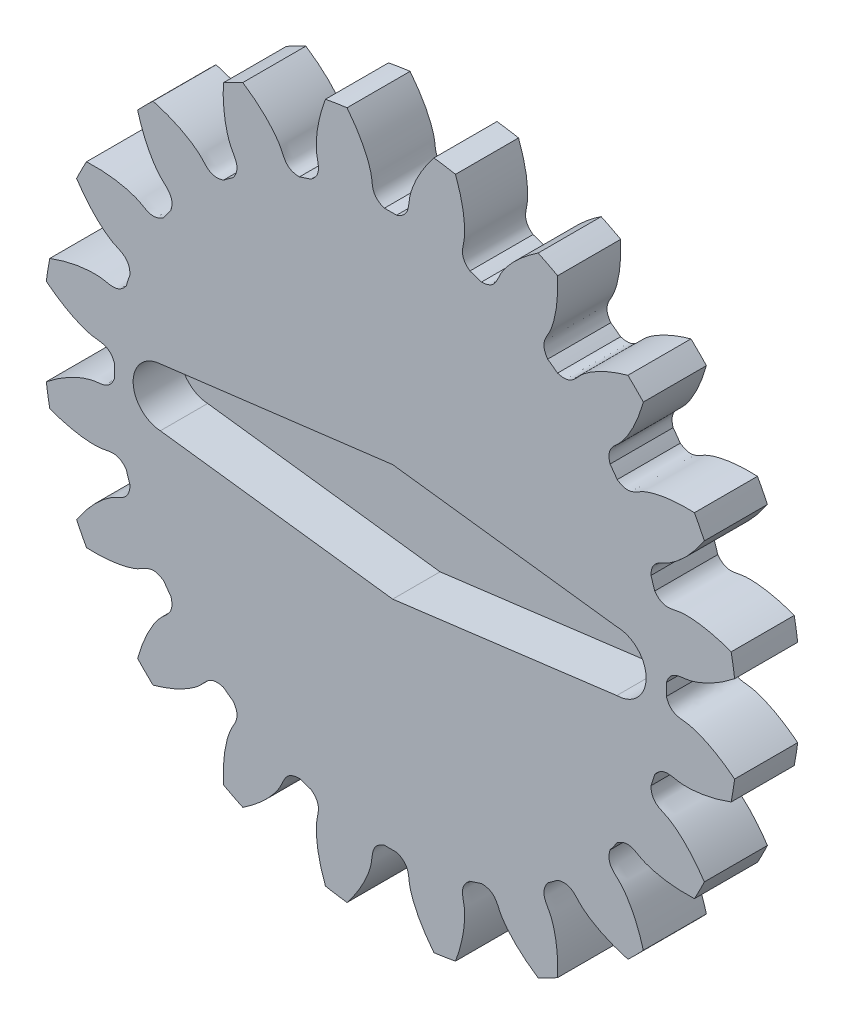
SolidWorks part; units mm, degrees
ref_plane "前视基准面" through (0, 0, 0) normal (0, 0, 1) x (1, 0, 0)
ref_plane "上视基准面" through (0, 0, 0) normal (0, 1, 0) x (1, 0, 0)
ref_plane "右视基准面" through (0, 0, 0) normal (1, 0, 0) x (0, 0, -1)
sketch "草图1" plane through (0, 0, 0) normal (0, 0, 1) x (1, 0, 0)
  circle A0 centre (0, 0) radius 22
extrude "凸台-拉伸1" add sketch "草图1" along normal blind 30
ref_axis "基准轴1" through (0, 0, -1.5) along (0, 0, 1)
sketch "草图2" plane through (0, 0, 0) normal (0, 0, 1) x (1, 0, 0)
  line L0 (0, 0) -> (0, 22) construction
  circle A0 centre (0, 0) radius 22 construction
  arc A1 (0.3866, 17.4957) -> (-0.3866, 17.4957) centre (0, 0) ccw
  arc A2 (6.3623, 24.9965) -> (-6.3623, 24.9965) centre (0, 0) ccw
  spline S0 degree 3 poles (0.3866, 17.4957) (1.2224, 17.787) (1.1142, 18.3742) (1.2258, 18.94) (1.2378, 18.9951) (1.2526, 19.0573) (1.2706, 19.1264) (1.292, 19.2024) (1.317, 19.2851) (1.3461, 19.3745) (1.3793, 19.4704) (1.4171, 19.5726) (1.4597, 19.6811) (1.5073, 19.7956) (1.5603, 19.9161) (1.6187, 20.0423) (1.683, 20.174) (1.7534, 20.3112) (1.83, 20.4535) (1.9132, 20.6008) (2.0031, 20.7529) (2.1, 20.9095) (2.204, 21.0705) (2.3155, 21.2356) (2.4346, 21.4046) (2.5615, 21.5772) (2.6964, 21.7533) (2.8395, 21.9324) (2.991, 22.1145) (3.1509, 22.2992) (3.3196, 22.4862) (3.4971, 22.6753) (3.6837, 22.8662) (3.8793, 23.0586) (4.0843, 23.2521) (4.2986, 23.4467) (4.5225, 23.6418) (4.7559, 23.8372) (4.9991, 24.0327) (5.2521, 24.2278) (5.515, 24.4223) (5.8829, 24.6833) (6.1679, 24.8727) (6.3623, 24.9965) knots 0 0 0 0 0.165916 0.170906 0.176664 0.183189 0.190482 0.198542 0.207371 0.216967 0.22733 0.238462 0.250361 0.263027 0.276462 0.290664 0.305634 0.321371 0.337876 0.355149 0.37319 0.391998 0.411574 0.431917 0.453028 0.474907 0.497554 0.520968 0.54515 0.570099 0.595817 0.622302 0.649554 0.677575 0.706363 0.735918 0.766242 0.797333 0.829191 0.861818 0.895212 0.929373 1 1 1 1
  spline S1 degree 3 poles (-0.3866, 17.4957) (-1.2224, 17.787) (-1.1142, 18.3742) (-1.2258, 18.94) (-1.2378, 18.9951) (-1.2526, 19.0573) (-1.2706, 19.1264) (-1.292, 19.2024) (-1.317, 19.2851) (-1.3461, 19.3745) (-1.3793, 19.4704) (-1.4171, 19.5726) (-1.4597, 19.6811) (-1.5073, 19.7956) (-1.5603, 19.9161) (-1.6187, 20.0423) (-1.683, 20.174) (-1.7534, 20.3112) (-1.83, 20.4535) (-1.9132, 20.6008) (-2.0031, 20.7529) (-2.1, 20.9095) (-2.204, 21.0705) (-2.3155, 21.2356) (-2.4346, 21.4046) (-2.5615, 21.5772) (-2.6964, 21.7533) (-2.8395, 21.9324) (-2.991, 22.1145) (-3.1509, 22.2992) (-3.3196, 22.4862) (-3.4971, 22.6753) (-3.6837, 22.8662) (-3.8793, 23.0586) (-4.0843, 23.2521) (-4.2986, 23.4467) (-4.5225, 23.6418) (-4.7559, 23.8372) (-4.9991, 24.0327) (-5.2521, 24.2278) (-5.515, 24.4223) (-5.8829, 24.6833) (-6.1679, 24.8727) (-6.3623, 24.9965) knots 0 0 0 0 0.165916 0.170906 0.176664 0.183189 0.190482 0.198542 0.207371 0.216967 0.22733 0.238462 0.250361 0.263027 0.276462 0.290664 0.305634 0.321371 0.337876 0.355149 0.37319 0.391998 0.411574 0.431917 0.453028 0.474907 0.497554 0.520968 0.54515 0.570099 0.595817 0.622302 0.649554 0.677575 0.706363 0.735918 0.766242 0.797333 0.829191 0.861818 0.895212 0.929373 1 1 1 1
extrude "切除-拉伸1" cut sketch "草图2" along normal through all
pattern_circular "阵列(圆周)1" count 20 every 18 about axis through (0, 0, -1.5) along (0, 0, 1) of "切除-拉伸1"
sketch "草图4" plane through (0, 0, 30) normal (0, 0, 1) x (1, 0, 0)
  line L0 (14.3305, 1.878) -> (0.1423, 3.6731)
  line L1 (0.1423, -3.7145) -> (14.354, -1.9038)
  line L2 (-14.5959, -1.8373) -> (0.1423, -3.7145)
  line L3 (0.1423, 3.6731) -> (-14.6311, 1.8342)
  circle A0 centre (0, 0) radius 0.8783 construction
  arc A1 (14.354, -1.9038) -> (14.3305, 1.878) centre (14.326, -0.013) ccw
  arc A2 (-14.6311, 1.8342) -> (-14.5959, -1.8373) centre (-14.4818, -0.0003) ccw
extrude "切除-拉伸2" cut sketch "草图4" against normal blind 3
sketch "草图6" plane through (0, 0, 0) normal (0, 0, -1) x (-1, 0, 0)
  arc A40 (5.7742, 16.52) -> (5.0388, 16.7589) centre (0, 0) ccw
  arc A41 (4.1243, 21.61) -> (2.7554, 21.8268) centre (0, 0) ccw
  arc A42 (0.3866, 17.4957) -> (-0.3866, 17.4957) centre (0, 0) ccw
  arc A43 (-2.7554, 21.8268) -> (-4.1243, 21.61) centre (0, 0) ccw
  arc A44 (-5.0388, 16.7589) -> (-5.7742, 16.52) centre (0, 0) ccw
  arc A45 (-9.3654, 19.907) -> (-10.6003, 19.2778) centre (0, 0) ccw
  arc A46 (-9.9709, 14.3816) -> (-10.5965, 13.9271) centre (0, 0) ccw
  arc A47 (-15.0586, 16.0386) -> (-16.0386, 15.0586) centre (0, 0) ccw
  arc A48 (-13.9271, 10.5965) -> (-14.3816, 9.9709) centre (0, 0) ccw
  arc A49 (-19.2778, 10.6003) -> (-19.907, 9.3654) centre (0, 0) ccw
  arc A50 (-16.52, 5.7742) -> (-16.7589, 5.0388) centre (0, 0) ccw
  arc A51 (-21.61, 4.1243) -> (-21.8268, 2.7554) centre (0, 0) ccw
  arc A52 (-17.4957, 0.3866) -> (-17.4957, -0.3866) centre (0, 0) ccw
  arc A53 (-21.8268, -2.7554) -> (-21.61, -4.1243) centre (0, 0) ccw
  arc A54 (-16.7589, -5.0388) -> (-16.52, -5.7742) centre (0, 0) ccw
  arc A55 (-19.907, -9.3654) -> (-19.2778, -10.6003) centre (0, 0) ccw
  arc A56 (-14.3816, -9.9709) -> (-13.9271, -10.5965) centre (0, 0) ccw
  arc A57 (-16.0386, -15.0586) -> (-15.0586, -16.0386) centre (0, 0) ccw
  arc A58 (-10.5965, -13.9271) -> (-9.9709, -14.3816) centre (0, 0) ccw
  arc A59 (-10.6003, -19.2778) -> (-9.3654, -19.907) centre (0, 0) ccw
  arc A60 (-5.7742, -16.52) -> (-5.0388, -16.7589) centre (0, 0) ccw
  arc A61 (-4.1243, -21.61) -> (-2.7554, -21.8268) centre (0, 0) ccw
  arc A62 (-0.3866, -17.4957) -> (0.3866, -17.4957) centre (0, 0) ccw
  arc A63 (2.7554, -21.8268) -> (4.1243, -21.61) centre (0, 0) ccw
  arc A64 (5.0388, -16.7589) -> (5.7742, -16.52) centre (0, 0) ccw
  arc A65 (9.3654, -19.907) -> (10.6003, -19.2778) centre (0, 0) ccw
  arc A66 (9.9709, -14.3816) -> (10.5965, -13.9271) centre (0, 0) ccw
  arc A67 (15.0586, -16.0386) -> (16.0386, -15.0586) centre (0, 0) ccw
  arc A68 (13.9271, -10.5965) -> (14.3816, -9.9709) centre (0, 0) ccw
  arc A69 (19.2778, -10.6003) -> (19.907, -9.3654) centre (0, 0) ccw
  arc A70 (16.52, -5.7742) -> (16.7589, -5.0388) centre (0, 0) ccw
  arc A71 (21.61, -4.1243) -> (21.8268, -2.7554) centre (0, 0) ccw
  arc A72 (17.4957, -0.3866) -> (17.4957, 0.3866) centre (0, 0) ccw
  arc A73 (21.8268, 2.7554) -> (21.61, 4.1243) centre (0, 0) ccw
  arc A74 (16.7589, 5.0388) -> (16.52, 5.7742) centre (0, 0) ccw
  arc A75 (19.907, 9.3654) -> (19.2778, 10.6003) centre (0, 0) ccw
  arc A76 (14.3816, 9.9709) -> (13.9271, 10.5965) centre (0, 0) ccw
  arc A77 (16.0386, 15.0586) -> (15.0586, 16.0386) centre (0, 0) ccw
  arc A78 (10.5965, 13.9271) -> (9.9709, 14.3816) centre (0, 0) ccw
  arc A79 (10.6003, 19.2778) -> (9.3654, 19.907) centre (0, 0) ccw
  arc A80 (5.7742, 16.52) -> (5.0388, 16.7589) centre (0, 0) ccw
  arc A81 (4.1243, 21.61) -> (2.7554, 21.8268) centre (0, 0) ccw
  arc A82 (0.3866, 17.4957) -> (-0.3866, 17.4957) centre (0, 0) ccw
  arc A83 (-2.7554, 21.8268) -> (-4.1243, 21.61) centre (0, 0) ccw
  arc A84 (-5.0388, 16.7589) -> (-5.7742, 16.52) centre (0, 0) ccw
  arc A85 (-9.3654, 19.907) -> (-10.6003, 19.2778) centre (0, 0) ccw
  arc A86 (-9.9709, 14.3816) -> (-10.5965, 13.9271) centre (0, 0) ccw
  arc A87 (-15.0586, 16.0386) -> (-16.0386, 15.0586) centre (0, 0) ccw
  arc A88 (-13.9271, 10.5965) -> (-14.3816, 9.9709) centre (0, 0) ccw
  arc A89 (-19.2778, 10.6003) -> (-19.907, 9.3654) centre (0, 0) ccw
  arc A90 (-16.52, 5.7742) -> (-16.7589, 5.0388) centre (0, 0) ccw
  arc A91 (-21.61, 4.1243) -> (-21.8268, 2.7554) centre (0, 0) ccw
  arc A92 (-17.4957, 0.3866) -> (-17.4957, -0.3866) centre (0, 0) ccw
  arc A93 (-21.8268, -2.7554) -> (-21.61, -4.1243) centre (0, 0) ccw
  arc A94 (-16.7589, -5.0388) -> (-16.52, -5.7742) centre (0, 0) ccw
  arc A95 (-19.907, -9.3654) -> (-19.2778, -10.6003) centre (0, 0) ccw
  arc A96 (-14.3816, -9.9709) -> (-13.9271, -10.5965) centre (0, 0) ccw
  arc A97 (-16.0386, -15.0586) -> (-15.0586, -16.0386) centre (0, 0) ccw
  arc A98 (-10.5965, -13.9271) -> (-9.9709, -14.3816) centre (0, 0) ccw
  arc A99 (-10.6003, -19.2778) -> (-9.3654, -19.907) centre (0, 0) ccw
  arc A100 (-5.7742, -16.52) -> (-5.0388, -16.7589) centre (0, 0) ccw
  arc A101 (-4.1243, -21.61) -> (-2.7554, -21.8268) centre (0, 0) ccw
  arc A102 (-0.3866, -17.4957) -> (0.3866, -17.4957) centre (0, 0) ccw
  arc A103 (2.7554, -21.8268) -> (4.1243, -21.61) centre (0, 0) ccw
  arc A104 (5.0388, -16.7589) -> (5.7742, -16.52) centre (0, 0) ccw
  arc A105 (9.3654, -19.907) -> (10.6003, -19.2778) centre (0, 0) ccw
  arc A106 (9.9709, -14.3816) -> (10.5965, -13.9271) centre (0, 0) ccw
  arc A107 (15.0586, -16.0386) -> (16.0386, -15.0586) centre (0, 0) ccw
  arc A108 (13.9271, -10.5965) -> (14.3816, -9.9709) centre (0, 0) ccw
  arc A109 (19.2778, -10.6003) -> (19.907, -9.3654) centre (0, 0) ccw
  arc A110 (16.52, -5.7742) -> (16.7589, -5.0388) centre (0, 0) ccw
  arc A111 (21.61, -4.1243) -> (21.8268, -2.7554) centre (0, 0) ccw
  arc A112 (17.4957, -0.3866) -> (17.4957, 0.3866) centre (0, 0) ccw
  arc A113 (21.8268, 2.7554) -> (21.61, 4.1243) centre (0, 0) ccw
  arc A114 (16.7589, 5.0388) -> (16.52, 5.7742) centre (0, 0) ccw
  arc A115 (19.907, 9.3654) -> (19.2778, 10.6003) centre (0, 0) ccw
  arc A116 (14.3816, 9.9709) -> (13.9271, 10.5965) centre (0, 0) ccw
  arc A117 (16.0386, 15.0586) -> (15.0586, 16.0386) centre (0, 0) ccw
  arc A118 (10.5965, 13.9271) -> (9.9709, 14.3816) centre (0, 0) ccw
  arc A119 (10.6003, 19.2778) -> (9.3654, 19.907) centre (0, 0) ccw
  spline S40 degree 3 poles (-3708.45, 1494.5416) (204.688, -113.6332) (40.2969, 43.5606) (8.612, 19.3644) (8.3225, 19.1244) (8.1035, 18.9276) (7.9087, 18.7415) (7.7679, 18.5988) (7.6102, 18.4289) (7.4979, 18.3006) (7.3961, 18.1768) (7.3285, 18.0912) (7.2672, 18.0103) (7.212, 17.9343) (7.1626, 17.8633) (7.1188, 17.7976) (7.0702, 17.7216) (7.029, 17.6528) (2.9985, 10.4296) (41.0631, -19.5683) (-3336.3667, 2212.5854) knots -11.584275 -11.584275 -11.584275 -11.584275 0.546972 0.588426 0.62681 0.662124 0.678629 0.709336 0.723538 0.749639 0.761538 0.77267 0.783033 0.792629 0.801458 0.809518 0.816811 0.829094 0.834084 3.350705 3.350705 3.350705 3.350705 only from (9.3654, 19.907) to (5.7742, 16.52)
  spline S41 degree 3 poles (4000.4369, -171.0805) (-44.7285, 8.305) (3.7044, 10.1997) (4.6895, 18.413) (4.6966, 18.4929) (4.702, 18.5829) (4.7051, 18.6618) (4.7069, 18.7482) (4.7069, 18.8422) (4.7048, 18.9437) (4.7005, 19.0526) (4.6909, 19.2127) (4.671, 19.4311) (4.6338, 19.7144) (4.5802, 20.0256) (4.508, 20.3639) (4.4148, 20.7281) (4.2986, 21.1171) (-9.4722, 61.2884) (-246.7896, 19.6625) (3881.4649, -959.8769) knots -2.350858 -2.350858 -2.350858 -2.350858 0.165916 0.170906 0.183189 0.190482 0.198542 0.207371 0.216967 0.22733 0.238462 0.250361 0.276462 0.305634 0.337876 0.37319 0.411574 0.453028 0.497554 13.418674 13.418674 13.418674 13.418674 only from (5.0388, 16.7589) to (4.1243, 21.61)
  spline S42 degree 3 poles (-3988.7843, 275.4194) (229.7845, -44.8196) (24.8636, 53.881) (2.2066, 21.0778) (2.0054, 20.7602) (1.8579, 20.5053) (1.7302, 20.2681) (1.6403, 20.0889) (1.5429, 19.8786) (1.4757, 19.7219) (1.4171, 19.5726) (1.3793, 19.4704) (1.3461, 19.3745) (1.317, 19.2851) (1.292, 19.2024) (1.2706, 19.1264) (1.2479, 19.0391) (1.2299, 18.9609) (-0.3711, 10.8457) (45.1002, -5.9213) (-3856.7998, 1073.2998) knots -11.584275 -11.584275 -11.584275 -11.584275 0.546972 0.588426 0.62681 0.662124 0.678629 0.709336 0.723538 0.749639 0.761538 0.77267 0.783033 0.792629 0.801458 0.809518 0.816811 0.829094 0.834084 3.350705 3.350705 3.350705 3.350705 only from (2.7554, 21.8268) to (0.3866, 17.4957)
  spline S43 degree 3 poles (3857.5084, 1073.4958) (-45.1057, -5.9234) (0.3712, 10.8453) (-1.2299, 18.9609) (-1.2479, 19.0391) (-1.2706, 19.1264) (-1.292, 19.2024) (-1.317, 19.2851) (-1.3461, 19.3745) (-1.3793, 19.4704) (-1.4171, 19.5726) (-1.4757, 19.7219) (-1.5621, 19.9235) (-1.6851, 20.1814) (-1.8322, 20.4609) (-2.0054, 20.7602) (-2.2066, 21.0778) (-2.4373, 21.4119) (-27.9477, 55.3617) (-240.7869, -57.562) (3988.1108, 286.5414) knots -2.350858 -2.350858 -2.350858 -2.350858 0.165916 0.170906 0.183189 0.190482 0.198542 0.207371 0.216967 0.22733 0.238462 0.250361 0.276462 0.305634 0.337876 0.37319 0.411574 0.453028 0.497554 13.418674 13.418674 13.418674 13.418674 only from (-0.3866, 17.4957) to (-2.7554, 21.8268)
  spline S44 degree 3 poles (-3878.6685, -970.6627) (232.388, 28.3814) (6.9966, 58.9272) (-4.4148, 20.7281) (-4.508, 20.3639) (-4.5695, 20.0759) (-4.6177, 19.8108) (-4.6478, 19.6126) (-4.6755, 19.3824) (-4.6909, 19.2127) (-4.7005, 19.0526) (-4.7048, 18.9437) (-4.7069, 18.8422) (-4.7069, 18.7482) (-4.7051, 18.6618) (-4.702, 18.5829) (-4.6966, 18.4929) (-4.6895, 18.413) (-3.7045, 10.2002) (44.7226, 8.3052) (-3999.7024, -171.0479) knots -11.584275 -11.584275 -11.584275 -11.584275 0.546972 0.588426 0.62681 0.662124 0.678629 0.709336 0.723538 0.749639 0.761538 0.77267 0.783033 0.792629 0.801458 0.809518 0.816811 0.829094 0.834084 3.350705 3.350705 3.350705 3.350705 only from (-4.1243, 21.61) to (-5.0388, 16.7589)
  spline S45 degree 3 poles (3336.9801, 2212.9908) (-41.0677, -19.5719) (-2.9983, 10.4292) (-7.029, 17.6528) (-7.0702, 17.7216) (-7.1188, 17.7976) (-7.1626, 17.8633) (-7.212, 17.9343) (-7.2672, 18.0103) (-7.3285, 18.0912) (-7.3961, 18.1768) (-7.4979, 18.3006) (-7.6424, 18.4656) (-7.839, 18.673) (-8.0653, 18.8932) (-8.3225, 19.1244) (-8.612, 19.3644) (-8.9347, 19.6108) (-43.6876, 44.0158) (-211.2143, -129.152) (3704.3726, 1504.9111) knots -2.350858 -2.350858 -2.350858 -2.350858 0.165916 0.170906 0.183189 0.190482 0.198542 0.207371 0.216967 0.22733 0.238462 0.250361 0.276462 0.305634 0.337876 0.37319 0.411574 0.453028 0.497554 13.418674 13.418674 13.418674 13.418674 only from (-5.7742, 16.52) to (-9.3654, 19.907)
  spline S46 degree 3 poles (-3388.8817, -2121.7296) (212.2438, 98.8041) (-11.5554, 58.2051) (-10.6041, 18.3493) (-10.5801, 17.9741) (-10.5496, 17.6812) (-10.5135, 17.4143) (-10.4809, 17.2164) (-10.4361, 16.989) (-10.3984, 16.8228) (-10.358, 16.6676) (-10.3285, 16.5626) (-10.2991, 16.4655) (-10.27, 16.3761) (-10.2417, 16.2944) (-10.2143, 16.2204) (-10.1813, 16.1364) (-10.1499, 16.0626) (-6.6752, 8.5562) (39.9673, 21.7188) (-3751.0863, -1398.6523) knots -11.584275 -11.584275 -11.584275 -11.584275 0.546972 0.588426 0.62681 0.662124 0.678629 0.709336 0.723538 0.749639 0.761538 0.77267 0.783033 0.792629 0.801458 0.809518 0.816811 0.829094 0.834084 3.350705 3.350705 3.350705 3.350705 only from (-10.6003, 19.2778) to (-9.9709, 14.3816)
  spline S47 degree 3 poles (2489.8049, 3135.8629) (-33.0096, -31.3046) (-6.0743, 8.9922) (-12.14, 14.6168) (-12.2005, 14.6694) (-12.2701, 14.7267) (-12.3321, 14.7757) (-12.401, 14.8279) (-12.477, 14.8831) (-12.5603, 14.9411) (-12.651, 15.0016) (-12.7861, 15.088) (-12.9745, 15.2003) (-13.2256, 15.3367) (-13.5089, 15.4762) (-13.825, 15.6166) (-14.1744, 15.7553) (-14.5574, 15.89) (-55.151, 28.3613) (-160.9666, -188.0996) (3058.0245, 2575.9696) knots -2.350858 -2.350858 -2.350858 -2.350858 0.165916 0.170906 0.183189 0.190482 0.198542 0.207371 0.216967 0.22733 0.238462 0.250361 0.276462 0.305634 0.337876 0.37319 0.411574 0.453028 0.497554 13.418674 13.418674 13.418674 13.418674 only from (-10.5965, 13.9271) to (-15.0586, 16.0386)
  spline S48 degree 3 poles (-2567.3676, -3065.1068) (171.3237, 159.5553) (-28.9762, 51.7856) (-15.7553, 14.1744) (-15.6166, 13.825) (-15.4971, 13.5558) (-15.3803, 13.3131) (-15.2881, 13.135) (-15.1752, 12.9325) (-15.088, 12.7861) (-15.0016, 12.651) (-14.9411, 12.5603) (-14.8831, 12.477) (-14.8279, 12.401) (-14.7757, 12.3321) (-14.7267, 12.2701) (-14.6694, 12.2005) (-14.6168, 12.14) (-8.9925, 6.0747) (31.2997, 33.0064) (-3135.2878, -2489.3468) knots -11.584275 -11.584275 -11.584275 -11.584275 0.546972 0.588426 0.62681 0.662124 0.678629 0.709336 0.723538 0.749639 0.761538 0.77267 0.783033 0.792629 0.801458 0.809518 0.816811 0.829094 0.834084 3.350705 3.350705 3.350705 3.350705 only from (-16.0386, 15.0586) to (-13.9271, 10.5965)
  spline S49 degree 3 poles (1398.9102, 3751.7748) (-21.7204, -39.973) (-8.5558, 6.675) (-16.0626, 10.1499) (-16.1364, 10.1813) (-16.2204, 10.2143) (-16.2944, 10.2417) (-16.3761, 10.27) (-16.4655, 10.2991) (-16.5626, 10.3285) (-16.6676, 10.358) (-16.8228, 10.3984) (-17.0366, 10.447) (-17.3176, 10.4991) (-17.6301, 10.5443) (-17.9741, 10.5801) (-18.3493, 10.6041) (-18.7552, 10.6138) (-61.2158, 9.9306) (-94.9623, -228.6348) (2112.3358, 3394.8742) knots -2.350858 -2.350858 -2.350858 -2.350858 0.165916 0.170906 0.183189 0.190482 0.198542 0.207371 0.216967 0.22733 0.238462 0.250361 0.276462 0.305634 0.337876 0.37319 0.411574 0.453028 0.497554 13.418674 13.418674 13.418674 13.418674 only from (-14.3816, 9.9709) to (-19.2778, 10.6003)
  spline S50 degree 3 poles (-1494.5416, -3708.45) (113.6332, 204.688) (-43.5606, 40.2969) (-19.3644, 8.612) (-19.1244, 8.3225) (-18.9276, 8.1035) (-18.7415, 7.9087) (-18.5988, 7.7679) (-18.4289, 7.6102) (-18.3006, 7.4979) (-18.1768, 7.3961) (-18.0912, 7.3285) (-18.0103, 7.2672) (-17.9343, 7.212) (-17.8633, 7.1626) (-17.7976, 7.1188) (-17.7216, 7.0702) (-17.6528, 7.029) (-10.4296, 2.9985) (19.5683, 41.0631) (-2212.5854, -3336.3667) knots -11.584275 -11.584275 -11.584275 -11.584275 0.546972 0.588426 0.62681 0.662124 0.678629 0.709336 0.723538 0.749639 0.761538 0.77267 0.783033 0.792629 0.801458 0.809518 0.816811 0.829094 0.834084 3.350705 3.350705 3.350705 3.350705 only from (-19.907, 9.3654) to (-16.52, 5.7742)
  spline S51 degree 3 poles (171.0805, 4000.4369) (-8.305, -44.7285) (-10.1997, 3.7044) (-18.413, 4.6895) (-18.4929, 4.6966) (-18.5829, 4.702) (-18.6618, 4.7051) (-18.7482, 4.7069) (-18.8422, 4.7069) (-18.9437, 4.7048) (-19.0526, 4.7005) (-19.2127, 4.6909) (-19.4311, 4.671) (-19.7144, 4.6338) (-20.0256, 4.5802) (-20.3639, 4.508) (-20.7281, 4.4148) (-21.1171, 4.2986) (-61.2884, -9.4722) (-19.6625, -246.7896) (959.8769, 3881.4649) knots -2.350858 -2.350858 -2.350858 -2.350858 0.165916 0.170906 0.183189 0.190482 0.198542 0.207371 0.216967 0.22733 0.238462 0.250361 0.276462 0.305634 0.337876 0.37319 0.411574 0.453028 0.497554 13.418674 13.418674 13.418674 13.418674 only from (-16.7589, 5.0388) to (-21.61, 4.1243)
  spline S52 degree 3 poles (-275.4194, -3988.7843) (44.8196, 229.7845) (-53.881, 24.8636) (-21.0778, 2.2066) (-20.7602, 2.0054) (-20.5053, 1.8579) (-20.2681, 1.7302) (-20.0889, 1.6403) (-19.8786, 1.5429) (-19.7219, 1.4757) (-19.5726, 1.4171) (-19.4704, 1.3793) (-19.3745, 1.3461) (-19.2851, 1.317) (-19.2024, 1.292) (-19.1264, 1.2706) (-19.0391, 1.2479) (-18.9609, 1.2299) (-10.8457, -0.3711) (5.9213, 45.1002) (-1073.2998, -3856.7998) knots -11.584275 -11.584275 -11.584275 -11.584275 0.546972 0.588426 0.62681 0.662124 0.678629 0.709336 0.723538 0.749639 0.761538 0.77267 0.783033 0.792629 0.801458 0.809518 0.816811 0.829094 0.834084 3.350705 3.350705 3.350705 3.350705 only from (-21.8268, 2.7554) to (-17.4957, 0.3866)
  spline S53 degree 3 poles (-1073.4958, 3857.5084) (5.9234, -45.1057) (-10.8453, 0.3712) (-18.9609, -1.2299) (-19.0391, -1.2479) (-19.1264, -1.2706) (-19.2024, -1.292) (-19.2851, -1.317) (-19.3745, -1.3461) (-19.4704, -1.3793) (-19.5726, -1.4171) (-19.7219, -1.4757) (-19.9235, -1.5621) (-20.1814, -1.6851) (-20.4609, -1.8322) (-20.7602, -2.0054) (-21.0778, -2.2066) (-21.4119, -2.4373) (-55.3617, -27.9477) (57.562, -240.7869) (-286.5415, 3988.1108) knots -2.350858 -2.350858 -2.350858 -2.350858 0.165916 0.170906 0.183189 0.190482 0.198542 0.207371 0.216967 0.22733 0.238462 0.250361 0.276462 0.305634 0.337876 0.37319 0.411574 0.453028 0.497554 13.418674 13.418674 13.418674 13.418674 only from (-17.4957, -0.3866) to (-21.8268, -2.7554)
  spline S54 degree 3 poles (970.6627, -3878.6685) (-28.3814, 232.388) (-58.9272, 6.9966) (-20.7281, -4.4148) (-20.3639, -4.508) (-20.0759, -4.5695) (-19.8108, -4.6177) (-19.6126, -4.6478) (-19.3824, -4.6755) (-19.2127, -4.6909) (-19.0526, -4.7005) (-18.9437, -4.7048) (-18.8422, -4.7069) (-18.7482, -4.7069) (-18.6618, -4.7051) (-18.5829, -4.702) (-18.4929, -4.6966) (-18.413, -4.6895) (-10.2002, -3.7045) (-8.3052, 44.7226) (171.0479, -3999.7024) knots -11.584275 -11.584275 -11.584275 -11.584275 0.546972 0.588426 0.62681 0.662124 0.678629 0.709336 0.723538 0.749639 0.761538 0.77267 0.783033 0.792629 0.801458 0.809518 0.816811 0.829094 0.834084 3.350705 3.350705 3.350705 3.350705 only from (-21.61, -4.1243) to (-16.7589, -5.0388)
  spline S55 degree 3 poles (-2212.9908, 3336.9801) (19.5719, -41.0677) (-10.4292, -2.9983) (-17.6528, -7.029) (-17.7216, -7.0702) (-17.7976, -7.1188) (-17.8633, -7.1626) (-17.9343, -7.212) (-18.0103, -7.2672) (-18.0912, -7.3285) (-18.1768, -7.3961) (-18.3006, -7.4979) (-18.4656, -7.6424) (-18.673, -7.839) (-18.8932, -8.0653) (-19.1244, -8.3225) (-19.3644, -8.612) (-19.6108, -8.9347) (-44.0158, -43.6876) (129.152, -211.2143) (-1504.9111, 3704.3726) knots -2.350858 -2.350858 -2.350858 -2.350858 0.165916 0.170906 0.183189 0.190482 0.198542 0.207371 0.216967 0.22733 0.238462 0.250361 0.276462 0.305634 0.337876 0.37319 0.411574 0.453028 0.497554 13.418674 13.418674 13.418674 13.418674 only from (-16.52, -5.7742) to (-19.907, -9.3654)
  spline S56 degree 3 poles (2121.7296, -3388.8817) (-98.8041, 212.2438) (-58.2051, -11.5554) (-18.3493, -10.6041) (-17.9741, -10.5801) (-17.6812, -10.5496) (-17.4143, -10.5135) (-17.2164, -10.4809) (-16.989, -10.4361) (-16.8228, -10.3984) (-16.6676, -10.358) (-16.5626, -10.3285) (-16.4655, -10.2991) (-16.3761, -10.27) (-16.2944, -10.2417) (-16.2204, -10.2143) (-16.1364, -10.1813) (-16.0626, -10.1499) (-8.5562, -6.6752) (-21.7188, 39.9673) (1398.6523, -3751.0863) knots -11.584275 -11.584275 -11.584275 -11.584275 0.546972 0.588426 0.62681 0.662124 0.678629 0.709336 0.723538 0.749639 0.761538 0.77267 0.783033 0.792629 0.801458 0.809518 0.816811 0.829094 0.834084 3.350705 3.350705 3.350705 3.350705 only from (-19.2778, -10.6003) to (-14.3816, -9.9709)
  spline S57 degree 3 poles (-3135.8629, 2489.8049) (31.3046, -33.0096) (-8.9922, -6.0743) (-14.6168, -12.14) (-14.6694, -12.2005) (-14.7267, -12.2701) (-14.7757, -12.3321) (-14.8279, -12.401) (-14.8831, -12.477) (-14.9411, -12.5603) (-15.0016, -12.651) (-15.088, -12.7861) (-15.2003, -12.9745) (-15.3367, -13.2256) (-15.4762, -13.5089) (-15.6166, -13.825) (-15.7553, -14.1744) (-15.89, -14.5574) (-28.3613, -55.151) (188.0996, -160.9666) (-2575.9696, 3058.0245) knots -2.350858 -2.350858 -2.350858 -2.350858 0.165916 0.170906 0.183189 0.190482 0.198542 0.207371 0.216967 0.22733 0.238462 0.250361 0.276462 0.305634 0.337876 0.37319 0.411574 0.453028 0.497554 13.418674 13.418674 13.418674 13.418674 only from (-13.9271, -10.5965) to (-16.0386, -15.0586)
  spline S58 degree 3 poles (3065.1068, -2567.3676) (-159.5553, 171.3237) (-51.7856, -28.9762) (-14.1744, -15.7553) (-13.825, -15.6166) (-13.5558, -15.4971) (-13.3131, -15.3803) (-13.135, -15.2881) (-12.9325, -15.1752) (-12.7861, -15.088) (-12.651, -15.0016) (-12.5603, -14.9411) (-12.477, -14.8831) (-12.401, -14.8279) (-12.3321, -14.7757) (-12.2701, -14.7267) (-12.2005, -14.6694) (-12.14, -14.6168) (-6.0747, -8.9925) (-33.0064, 31.2997) (2489.3468, -3135.2878) knots -11.584275 -11.584275 -11.584275 -11.584275 0.546972 0.588426 0.62681 0.662124 0.678629 0.709336 0.723538 0.749639 0.761538 0.77267 0.783033 0.792629 0.801458 0.809518 0.816811 0.829094 0.834084 3.350705 3.350705 3.350705 3.350705 only from (-15.0586, -16.0386) to (-10.5965, -13.9271)
  spline S59 degree 3 poles (-3751.7748, 1398.9102) (39.973, -21.7204) (-6.675, -8.5558) (-10.1499, -16.0626) (-10.1813, -16.1364) (-10.2143, -16.2204) (-10.2417, -16.2944) (-10.27, -16.3761) (-10.2991, -16.4655) (-10.3285, -16.5626) (-10.358, -16.6676) (-10.3984, -16.8228) (-10.447, -17.0366) (-10.4991, -17.3176) (-10.5443, -17.6301) (-10.5801, -17.9741) (-10.6041, -18.3493) (-10.6138, -18.7552) (-9.9306, -61.2158) (228.6348, -94.9623) (-3394.8742, 2112.3358) knots -2.350858 -2.350858 -2.350858 -2.350858 0.165916 0.170906 0.183189 0.190482 0.198542 0.207371 0.216967 0.22733 0.238462 0.250361 0.276462 0.305634 0.337876 0.37319 0.411574 0.453028 0.497554 13.418674 13.418674 13.418674 13.418674 only from (-9.9709, -14.3816) to (-10.6003, -19.2778)
  spline S60 degree 3 poles (3708.45, -1494.5416) (-204.688, 113.6332) (-40.2969, -43.5606) (-8.612, -19.3644) (-8.3225, -19.1244) (-8.1035, -18.9276) (-7.9087, -18.7415) (-7.7679, -18.5988) (-7.6102, -18.4289) (-7.4979, -18.3006) (-7.3961, -18.1768) (-7.3285, -18.0912) (-7.2672, -18.0103) (-7.212, -17.9343) (-7.1626, -17.8633) (-7.1188, -17.7976) (-7.0702, -17.7216) (-7.029, -17.6528) (-2.9985, -10.4296) (-41.0631, 19.5683) (3336.3667, -2212.5854) knots -11.584275 -11.584275 -11.584275 -11.584275 0.546972 0.588426 0.62681 0.662124 0.678629 0.709336 0.723538 0.749639 0.761538 0.77267 0.783033 0.792629 0.801458 0.809518 0.816811 0.829094 0.834084 3.350705 3.350705 3.350705 3.350705 only from (-9.3654, -19.907) to (-5.7742, -16.52)
  spline S61 degree 3 poles (-4000.4369, 171.0805) (44.7285, -8.305) (-3.7044, -10.1997) (-4.6895, -18.413) (-4.6966, -18.4929) (-4.702, -18.5829) (-4.7051, -18.6618) (-4.7069, -18.7482) (-4.7069, -18.8422) (-4.7048, -18.9437) (-4.7005, -19.0526) (-4.6909, -19.2127) (-4.671, -19.4311) (-4.6338, -19.7144) (-4.5802, -20.0256) (-4.508, -20.3639) (-4.4148, -20.7281) (-4.2986, -21.1171) (9.4722, -61.2884) (246.7896, -19.6625) (-3881.4649, 959.8769) knots -2.350858 -2.350858 -2.350858 -2.350858 0.165916 0.170906 0.183189 0.190482 0.198542 0.207371 0.216967 0.22733 0.238462 0.250361 0.276462 0.305634 0.337876 0.37319 0.411574 0.453028 0.497554 13.418674 13.418674 13.418674 13.418674 only from (-5.0388, -16.7589) to (-4.1243, -21.61)
  spline S62 degree 3 poles (3988.7843, -275.4194) (-229.7845, 44.8196) (-24.8636, -53.881) (-2.2066, -21.0778) (-2.0054, -20.7602) (-1.8579, -20.5053) (-1.7302, -20.2681) (-1.6403, -20.0889) (-1.5429, -19.8786) (-1.4757, -19.7219) (-1.4171, -19.5726) (-1.3793, -19.4704) (-1.3461, -19.3745) (-1.317, -19.2851) (-1.292, -19.2024) (-1.2706, -19.1264) (-1.2479, -19.0391) (-1.2299, -18.9609) (0.3711, -10.8457) (-45.1002, 5.9213) (3856.7998, -1073.2998) knots -11.584275 -11.584275 -11.584275 -11.584275 0.546972 0.588426 0.62681 0.662124 0.678629 0.709336 0.723538 0.749639 0.761538 0.77267 0.783033 0.792629 0.801458 0.809518 0.816811 0.829094 0.834084 3.350705 3.350705 3.350705 3.350705 only from (-2.7554, -21.8268) to (-0.3866, -17.4957)
  spline S63 degree 3 poles (-3857.5084, -1073.4958) (45.1057, 5.9234) (-0.3712, -10.8453) (1.2299, -18.9609) (1.2479, -19.0391) (1.2706, -19.1264) (1.292, -19.2024) (1.317, -19.2851) (1.3461, -19.3745) (1.3793, -19.4704) (1.4171, -19.5726) (1.4757, -19.7219) (1.5621, -19.9235) (1.6851, -20.1814) (1.8322, -20.4609) (2.0054, -20.7602) (2.2066, -21.0778) (2.4373, -21.4119) (27.9477, -55.3617) (240.7869, 57.562) (-3988.1108, -286.5414) knots -2.350858 -2.350858 -2.350858 -2.350858 0.165916 0.170906 0.183189 0.190482 0.198542 0.207371 0.216967 0.22733 0.238462 0.250361 0.276462 0.305634 0.337876 0.37319 0.411574 0.453028 0.497554 13.418674 13.418674 13.418674 13.418674 only from (0.3866, -17.4957) to (2.7554, -21.8268)
  spline S64 degree 3 poles (3878.6685, 970.6627) (-232.388, -28.3814) (-6.9966, -58.9272) (4.4148, -20.7281) (4.508, -20.3639) (4.5695, -20.0759) (4.6177, -19.8108) (4.6478, -19.6126) (4.6755, -19.3824) (4.6909, -19.2127) (4.7005, -19.0526) (4.7048, -18.9437) (4.7069, -18.8422) (4.7069, -18.7482) (4.7051, -18.6618) (4.702, -18.5829) (4.6966, -18.4929) (4.6895, -18.413) (3.7045, -10.2002) (-44.7226, -8.3052) (3999.7024, 171.0479) knots -11.584275 -11.584275 -11.584275 -11.584275 0.546972 0.588426 0.62681 0.662124 0.678629 0.709336 0.723538 0.749639 0.761538 0.77267 0.783033 0.792629 0.801458 0.809518 0.816811 0.829094 0.834084 3.350705 3.350705 3.350705 3.350705 only from (4.1243, -21.61) to (5.0388, -16.7589)
  spline S65 degree 3 poles (-3336.9801, -2212.9908) (41.0677, 19.5719) (2.9983, -10.4292) (7.029, -17.6528) (7.0702, -17.7216) (7.1188, -17.7976) (7.1626, -17.8633) (7.212, -17.9343) (7.2672, -18.0103) (7.3285, -18.0912) (7.3961, -18.1768) (7.4979, -18.3006) (7.6424, -18.4656) (7.839, -18.673) (8.0653, -18.8932) (8.3225, -19.1244) (8.612, -19.3644) (8.9347, -19.6108) (43.6876, -44.0158) (211.2143, 129.152) (-3704.3726, -1504.9111) knots -2.350858 -2.350858 -2.350858 -2.350858 0.165916 0.170906 0.183189 0.190482 0.198542 0.207371 0.216967 0.22733 0.238462 0.250361 0.276462 0.305634 0.337876 0.37319 0.411574 0.453028 0.497554 13.418674 13.418674 13.418674 13.418674 only from (5.7742, -16.52) to (9.3654, -19.907)
  spline S66 degree 3 poles (3388.8817, 2121.7296) (-212.2438, -98.8041) (11.5554, -58.2051) (10.6041, -18.3493) (10.5801, -17.9741) (10.5496, -17.6812) (10.5135, -17.4143) (10.4809, -17.2164) (10.4361, -16.989) (10.3984, -16.8228) (10.358, -16.6676) (10.3285, -16.5626) (10.2991, -16.4655) (10.27, -16.3761) (10.2417, -16.2944) (10.2143, -16.2204) (10.1813, -16.1364) (10.1499, -16.0626) (6.6752, -8.5562) (-39.9673, -21.7188) (3751.0863, 1398.6523) knots -11.584275 -11.584275 -11.584275 -11.584275 0.546972 0.588426 0.62681 0.662124 0.678629 0.709336 0.723538 0.749639 0.761538 0.77267 0.783033 0.792629 0.801458 0.809518 0.816811 0.829094 0.834084 3.350705 3.350705 3.350705 3.350705 only from (10.6003, -19.2778) to (9.9709, -14.3816)
  spline S67 degree 3 poles (-2489.8049, -3135.8629) (33.0096, 31.3046) (6.0743, -8.9922) (12.14, -14.6168) (12.2005, -14.6694) (12.2701, -14.7267) (12.3321, -14.7757) (12.401, -14.8279) (12.477, -14.8831) (12.5603, -14.9411) (12.651, -15.0016) (12.7861, -15.088) (12.9745, -15.2003) (13.2256, -15.3367) (13.5089, -15.4762) (13.825, -15.6166) (14.1744, -15.7553) (14.5574, -15.89) (55.151, -28.3613) (160.9666, 188.0996) (-3058.0246, -2575.9696) knots -2.350858 -2.350858 -2.350858 -2.350858 0.165916 0.170906 0.183189 0.190482 0.198542 0.207371 0.216967 0.22733 0.238462 0.250361 0.276462 0.305634 0.337876 0.37319 0.411574 0.453028 0.497554 13.418674 13.418674 13.418674 13.418674 only from (10.5965, -13.9271) to (15.0586, -16.0386)
  spline S68 degree 3 poles (2567.3676, 3065.1068) (-171.3237, -159.5553) (28.9762, -51.7856) (15.7553, -14.1744) (15.6166, -13.825) (15.4971, -13.5558) (15.3803, -13.3131) (15.2881, -13.135) (15.1752, -12.9325) (15.088, -12.7861) (15.0016, -12.651) (14.9411, -12.5603) (14.8831, -12.477) (14.8279, -12.401) (14.7757, -12.3321) (14.7267, -12.2701) (14.6694, -12.2005) (14.6168, -12.14) (8.9925, -6.0747) (-31.2997, -33.0064) (3135.2878, 2489.3468) knots -11.584275 -11.584275 -11.584275 -11.584275 0.546972 0.588426 0.62681 0.662124 0.678629 0.709336 0.723538 0.749639 0.761538 0.77267 0.783033 0.792629 0.801458 0.809518 0.816811 0.829094 0.834084 3.350705 3.350705 3.350705 3.350705 only from (16.0386, -15.0586) to (13.9271, -10.5965)
  spline S69 degree 3 poles (-1398.9102, -3751.7748) (21.7204, 39.973) (8.5558, -6.675) (16.0626, -10.1499) (16.1364, -10.1813) (16.2204, -10.2143) (16.2944, -10.2417) (16.3761, -10.27) (16.4655, -10.2991) (16.5626, -10.3285) (16.6676, -10.358) (16.8228, -10.3984) (17.0366, -10.447) (17.3176, -10.4991) (17.6301, -10.5443) (17.9741, -10.5801) (18.3493, -10.6041) (18.7552, -10.6138) (61.2158, -9.9306) (94.9623, 228.6348) (-2112.3358, -3394.8742) knots -2.350858 -2.350858 -2.350858 -2.350858 0.165916 0.170906 0.183189 0.190482 0.198542 0.207371 0.216967 0.22733 0.238462 0.250361 0.276462 0.305634 0.337876 0.37319 0.411574 0.453028 0.497554 13.418674 13.418674 13.418674 13.418674 only from (14.3816, -9.9709) to (19.2778, -10.6003)
  spline S70 degree 3 poles (1494.5416, 3708.45) (-113.6332, -204.688) (43.5606, -40.2969) (19.3644, -8.612) (19.1244, -8.3225) (18.9276, -8.1035) (18.7415, -7.9087) (18.5988, -7.7679) (18.4289, -7.6102) (18.3006, -7.4979) (18.1768, -7.3961) (18.0912, -7.3285) (18.0103, -7.2672) (17.9343, -7.212) (17.8633, -7.1626) (17.7976, -7.1188) (17.7216, -7.0702) (17.6528, -7.029) (10.4296, -2.9985) (-19.5683, -41.0631) (2212.5854, 3336.3667) knots -11.584275 -11.584275 -11.584275 -11.584275 0.546972 0.588426 0.62681 0.662124 0.678629 0.709336 0.723538 0.749639 0.761538 0.77267 0.783033 0.792629 0.801458 0.809518 0.816811 0.829094 0.834084 3.350705 3.350705 3.350705 3.350705 only from (19.907, -9.3654) to (16.52, -5.7742)
  spline S71 degree 3 poles (-171.0805, -4000.4369) (8.305, 44.7285) (10.1997, -3.7044) (18.413, -4.6895) (18.4929, -4.6966) (18.5829, -4.702) (18.6618, -4.7051) (18.7482, -4.7069) (18.8422, -4.7069) (18.9437, -4.7048) (19.0526, -4.7005) (19.2127, -4.6909) (19.4311, -4.671) (19.7144, -4.6338) (20.0256, -4.5802) (20.3639, -4.508) (20.7281, -4.4148) (21.1171, -4.2986) (61.2884, 9.4722) (19.6625, 246.7896) (-959.8769, -3881.4649) knots -2.350858 -2.350858 -2.350858 -2.350858 0.165916 0.170906 0.183189 0.190482 0.198542 0.207371 0.216967 0.22733 0.238462 0.250361 0.276462 0.305634 0.337876 0.37319 0.411574 0.453028 0.497554 13.418674 13.418674 13.418674 13.418674 only from (16.7589, -5.0388) to (21.61, -4.1243)
  spline S72 degree 3 poles (275.4194, 3988.7843) (-44.8196, -229.7845) (53.881, -24.8636) (21.0778, -2.2066) (20.7602, -2.0054) (20.5053, -1.8579) (20.2681, -1.7302) (20.0889, -1.6403) (19.8786, -1.5429) (19.7219, -1.4757) (19.5726, -1.4171) (19.4704, -1.3793) (19.3745, -1.3461) (19.2851, -1.317) (19.2024, -1.292) (19.1264, -1.2706) (19.0391, -1.2479) (18.9609, -1.2299) (10.8457, 0.3711) (-5.9213, -45.1002) (1073.2998, 3856.7998) knots -11.584275 -11.584275 -11.584275 -11.584275 0.546972 0.588426 0.62681 0.662124 0.678629 0.709336 0.723538 0.749639 0.761538 0.77267 0.783033 0.792629 0.801458 0.809518 0.816811 0.829094 0.834084 3.350705 3.350705 3.350705 3.350705 only from (21.8268, -2.7554) to (17.4957, -0.3866)
  spline S73 degree 3 poles (1073.4958, -3857.5084) (-5.9234, 45.1057) (10.8453, -0.3712) (18.9609, 1.2299) (19.0391, 1.2479) (19.1264, 1.2706) (19.2024, 1.292) (19.2851, 1.317) (19.3745, 1.3461) (19.4704, 1.3793) (19.5726, 1.4171) (19.7219, 1.4757) (19.9235, 1.5621) (20.1814, 1.6851) (20.4609, 1.8322) (20.7602, 2.0054) (21.0778, 2.2066) (21.4119, 2.4373) (55.3617, 27.9477) (-57.562, 240.7869) (286.5414, -3988.1108) knots -2.350858 -2.350858 -2.350858 -2.350858 0.165916 0.170906 0.183189 0.190482 0.198542 0.207371 0.216967 0.22733 0.238462 0.250361 0.276462 0.305634 0.337876 0.37319 0.411574 0.453028 0.497554 13.418674 13.418674 13.418674 13.418674 only from (17.4957, 0.3866) to (21.8268, 2.7554)
  spline S74 degree 3 poles (-970.6627, 3878.6685) (28.3814, -232.388) (58.9272, -6.9966) (20.7281, 4.4148) (20.3639, 4.508) (20.0759, 4.5695) (19.8108, 4.6177) (19.6126, 4.6478) (19.3824, 4.6755) (19.2127, 4.6909) (19.0526, 4.7005) (18.9437, 4.7048) (18.8422, 4.7069) (18.7482, 4.7069) (18.6618, 4.7051) (18.5829, 4.702) (18.4929, 4.6966) (18.413, 4.6895) (10.2002, 3.7045) (8.3052, -44.7226) (-171.0479, 3999.7024) knots -11.584275 -11.584275 -11.584275 -11.584275 0.546972 0.588426 0.62681 0.662124 0.678629 0.709336 0.723538 0.749639 0.761538 0.77267 0.783033 0.792629 0.801458 0.809518 0.816811 0.829094 0.834084 3.350705 3.350705 3.350705 3.350705 only from (21.61, 4.1243) to (16.7589, 5.0388)
  spline S75 degree 3 poles (2212.9908, -3336.9801) (-19.5719, 41.0677) (10.4292, 2.9983) (17.6528, 7.029) (17.7216, 7.0702) (17.7976, 7.1188) (17.8633, 7.1626) (17.9343, 7.212) (18.0103, 7.2672) (18.0912, 7.3285) (18.1768, 7.3961) (18.3006, 7.4979) (18.4656, 7.6424) (18.673, 7.839) (18.8932, 8.0653) (19.1244, 8.3225) (19.3644, 8.612) (19.6108, 8.9347) (44.0158, 43.6876) (-129.152, 211.2143) (1504.9111, -3704.3726) knots -2.350858 -2.350858 -2.350858 -2.350858 0.165916 0.170906 0.183189 0.190482 0.198542 0.207371 0.216967 0.22733 0.238462 0.250361 0.276462 0.305634 0.337876 0.37319 0.411574 0.453028 0.497554 13.418674 13.418674 13.418674 13.418674 only from (16.52, 5.7742) to (19.907, 9.3654)
  spline S76 degree 3 poles (-2121.7296, 3388.8817) (98.8041, -212.2438) (58.2051, 11.5554) (18.3493, 10.6041) (17.9741, 10.5801) (17.6812, 10.5496) (17.4143, 10.5135) (17.2164, 10.4809) (16.989, 10.4361) (16.8228, 10.3984) (16.6676, 10.358) (16.5626, 10.3285) (16.4655, 10.2991) (16.3761, 10.27) (16.2944, 10.2417) (16.2204, 10.2143) (16.1364, 10.1813) (16.0626, 10.1499) (8.5562, 6.6752) (21.7188, -39.9673) (-1398.6523, 3751.0863) knots -11.584275 -11.584275 -11.584275 -11.584275 0.546972 0.588426 0.62681 0.662124 0.678629 0.709336 0.723538 0.749639 0.761538 0.77267 0.783033 0.792629 0.801458 0.809518 0.816811 0.829094 0.834084 3.350705 3.350705 3.350705 3.350705 only from (19.2778, 10.6003) to (14.3816, 9.9709)
  spline S77 degree 3 poles (3135.8629, -2489.8049) (-31.3046, 33.0096) (8.9922, 6.0743) (14.6168, 12.14) (14.6694, 12.2005) (14.7267, 12.2701) (14.7757, 12.3321) (14.8279, 12.401) (14.8831, 12.477) (14.9411, 12.5603) (15.0016, 12.651) (15.088, 12.7861) (15.2003, 12.9745) (15.3367, 13.2256) (15.4762, 13.5089) (15.6166, 13.825) (15.7553, 14.1744) (15.89, 14.5574) (28.3613, 55.151) (-188.0996, 160.9666) (2575.9696, -3058.0246) knots -2.350858 -2.350858 -2.350858 -2.350858 0.165916 0.170906 0.183189 0.190482 0.198542 0.207371 0.216967 0.22733 0.238462 0.250361 0.276462 0.305634 0.337876 0.37319 0.411574 0.453028 0.497554 13.418674 13.418674 13.418674 13.418674 only from (13.9271, 10.5965) to (16.0386, 15.0586)
  spline S78 degree 3 poles (-3065.1068, 2567.3676) (159.5553, -171.3237) (51.7856, 28.9762) (14.1744, 15.7553) (13.825, 15.6166) (13.5558, 15.4971) (13.3131, 15.3803) (13.135, 15.2881) (12.9325, 15.1752) (12.7861, 15.088) (12.651, 15.0016) (12.5603, 14.9411) (12.477, 14.8831) (12.401, 14.8279) (12.3321, 14.7757) (12.2701, 14.7267) (12.2005, 14.6694) (12.14, 14.6168) (6.0747, 8.9925) (33.0064, -31.2997) (-2489.3468, 3135.2878) knots -11.584275 -11.584275 -11.584275 -11.584275 0.546972 0.588426 0.62681 0.662124 0.678629 0.709336 0.723538 0.749639 0.761538 0.77267 0.783033 0.792629 0.801458 0.809518 0.816811 0.829094 0.834084 3.350705 3.350705 3.350705 3.350705 only from (15.0586, 16.0386) to (10.5965, 13.9271)
  spline S79 degree 3 poles (3751.7748, -1398.9102) (-39.973, 21.7204) (6.675, 8.5558) (10.1499, 16.0626) (10.1813, 16.1364) (10.2143, 16.2204) (10.2417, 16.2944) (10.27, 16.3761) (10.2991, 16.4655) (10.3285, 16.5626) (10.358, 16.6676) (10.3984, 16.8228) (10.447, 17.0366) (10.4991, 17.3176) (10.5443, 17.6301) (10.5801, 17.9741) (10.6041, 18.3493) (10.6138, 18.7552) (9.9306, 61.2158) (-228.6348, 94.9623) (3394.8742, -2112.3358) knots -2.350858 -2.350858 -2.350858 -2.350858 0.165916 0.170906 0.183189 0.190482 0.198542 0.207371 0.216967 0.22733 0.238462 0.250361 0.276462 0.305634 0.337876 0.37319 0.411574 0.453028 0.497554 13.418674 13.418674 13.418674 13.418674 only from (9.9709, 14.3816) to (10.6003, 19.2778)
  spline S80 degree 3 poles (9.3654, 19.907) (9.2173, 19.8091) (8.9603, 19.6304) (8.612, 19.3644) (8.3225, 19.1244) (8.1035, 18.9276) (7.9087, 18.7415) (7.7679, 18.5988) (7.6102, 18.4289) (7.4979, 18.3006) (7.3961, 18.1768) (7.3285, 18.0912) (7.2672, 18.0103) (7.212, 17.9343) (7.1626, 17.8633) (7.1188, 17.7976) (7.0702, 17.7216) (7.029, 17.6528) (6.7376, 17.1306) (6.659, 16.5387) (5.7742, 16.52) knots 0.492568 0.492568 0.492568 0.492568 0.546972 0.588426 0.62681 0.662124 0.678629 0.709336 0.723538 0.749639 0.761538 0.77267 0.783033 0.792629 0.801458 0.809518 0.816811 0.829094 0.834084 1 1 1 1
  spline S81 degree 3 poles (5.0388, 16.7589) (4.3339, 17.2941) (4.6183, 17.8192) (4.6895, 18.413) (4.6966, 18.4929) (4.702, 18.5829) (4.7051, 18.6618) (4.7069, 18.7482) (4.7069, 18.8422) (4.7048, 18.9437) (4.7005, 19.0526) (4.6909, 19.2127) (4.671, 19.4311) (4.6338, 19.7144) (4.5802, 20.0256) (4.508, 20.3639) (4.4148, 20.7281) (4.2986, 21.1171) (4.1971, 21.4132) (4.1356, 21.5798) (4.1243, 21.61) knots 0 0 0 0 0.165916 0.170906 0.183189 0.190482 0.198542 0.207371 0.216967 0.22733 0.238462 0.250361 0.276462 0.305634 0.337876 0.37319 0.411574 0.453028 0.497554 0.507432 0.507432 0.507432 0.507432
  spline S82 degree 3 poles (2.7554, 21.8268) (2.6448, 21.6878) (2.4556, 21.4385) (2.2066, 21.0778) (2.0054, 20.7602) (1.8579, 20.5053) (1.7302, 20.2681) (1.6403, 20.0889) (1.5429, 19.8786) (1.4757, 19.7219) (1.4171, 19.5726) (1.3793, 19.4704) (1.3461, 19.3745) (1.317, 19.2851) (1.292, 19.2024) (1.2706, 19.1264) (1.2479, 19.0391) (1.2299, 18.9609) (1.1142, 18.3742) (1.2224, 17.787) (0.3866, 17.4957) knots 0.492568 0.492568 0.492568 0.492568 0.546972 0.588426 0.62681 0.662124 0.678629 0.709336 0.723538 0.749639 0.761538 0.77267 0.783033 0.792629 0.801458 0.809518 0.816811 0.829094 0.834084 1 1 1 1
  spline S83 degree 3 poles (-0.3866, 17.4957) (-1.2224, 17.787) (-1.1142, 18.3742) (-1.2299, 18.9609) (-1.2479, 19.0391) (-1.2706, 19.1264) (-1.292, 19.2024) (-1.317, 19.2851) (-1.3461, 19.3745) (-1.3793, 19.4704) (-1.4171, 19.5726) (-1.4757, 19.7219) (-1.5621, 19.9235) (-1.6851, 20.1814) (-1.8322, 20.4609) (-2.0054, 20.7602) (-2.2066, 21.0778) (-2.4373, 21.4119) (-2.6253, 21.6621) (-2.7353, 21.8015) (-2.7554, 21.8268) knots 0 0 0 0 0.165916 0.170906 0.183189 0.190482 0.198542 0.207371 0.216967 0.22733 0.238462 0.250361 0.276462 0.305634 0.337876 0.37319 0.411574 0.453028 0.497554 0.507432 0.507432 0.507432 0.507432
  spline S84 degree 3 poles (-4.1243, 21.61) (-4.1865, 21.4436) (-4.2894, 21.148) (-4.4148, 20.7281) (-4.508, 20.3639) (-4.5695, 20.0759) (-4.6177, 19.8108) (-4.6478, 19.6126) (-4.6755, 19.3824) (-4.6909, 19.2127) (-4.7005, 19.0526) (-4.7048, 18.9437) (-4.7069, 18.8422) (-4.7069, 18.7482) (-4.7051, 18.6618) (-4.702, 18.5829) (-4.6966, 18.4929) (-4.6895, 18.413) (-4.6183, 17.8192) (-4.3339, 17.2941) (-5.0388, 16.7589) knots 0.492568 0.492568 0.492568 0.492568 0.546972 0.588426 0.62681 0.662124 0.678629 0.709336 0.723538 0.749639 0.761538 0.77267 0.783033 0.792629 0.801458 0.809518 0.816811 0.829094 0.834084 1 1 1 1
  spline S85 degree 3 poles (-5.7742, 16.52) (-6.659, 16.5387) (-6.7376, 17.1306) (-7.029, 17.6528) (-7.0702, 17.7216) (-7.1188, 17.7976) (-7.1626, 17.8633) (-7.212, 17.9343) (-7.2672, 18.0103) (-7.3285, 18.0912) (-7.3961, 18.1768) (-7.4979, 18.3006) (-7.6424, 18.4656) (-7.839, 18.673) (-8.0653, 18.8932) (-8.3225, 19.1244) (-8.612, 19.3644) (-8.9347, 19.6108) (-9.1908, 19.7906) (-9.3385, 19.8892) (-9.3654, 19.907) knots 0 0 0 0 0.165916 0.170906 0.183189 0.190482 0.198542 0.207371 0.216967 0.22733 0.238462 0.250361 0.276462 0.305634 0.337876 0.37319 0.411574 0.453028 0.497554 0.507432 0.507432 0.507432 0.507432
  spline S86 degree 3 poles (-10.6003, 19.2778) (-10.6081, 19.1004) (-10.6146, 18.7875) (-10.6041, 18.3493) (-10.5801, 17.9741) (-10.5496, 17.6812) (-10.5135, 17.4143) (-10.4809, 17.2164) (-10.4361, 16.989) (-10.3984, 16.8228) (-10.358, 16.6676) (-10.3285, 16.5626) (-10.2991, 16.4655) (-10.27, 16.3761) (-10.2417, 16.2944) (-10.2143, 16.2204) (-10.1813, 16.1364) (-10.1499, 16.0626) (-9.8987, 15.52) (-9.466, 15.1084) (-9.9709, 14.3816) knots 0.492568 0.492568 0.492568 0.492568 0.546972 0.588426 0.62681 0.662124 0.678629 0.709336 0.723538 0.749639 0.761538 0.77267 0.783033 0.792629 0.801458 0.809518 0.816811 0.829094 0.834084 1 1 1 1
  spline S87 degree 3 poles (-10.5965, 13.9271) (-11.4438, 13.6714) (-11.7015, 14.2102) (-12.14, 14.6168) (-12.2005, 14.6694) (-12.2701, 14.7267) (-12.3321, 14.7757) (-12.401, 14.8279) (-12.477, 14.8831) (-12.5603, 14.9411) (-12.651, 15.0016) (-12.7861, 15.088) (-12.9745, 15.2003) (-13.2256, 15.3367) (-13.5089, 15.4762) (-13.825, 15.6166) (-14.1744, 15.7553) (-14.5574, 15.89) (-14.8566, 15.9819) (-15.0275, 16.03) (-15.0586, 16.0386) knots 0 0 0 0 0.165916 0.170906 0.183189 0.190482 0.198542 0.207371 0.216967 0.22733 0.238462 0.250361 0.276462 0.305634 0.337876 0.37319 0.411574 0.453028 0.497554 0.507432 0.507432 0.507432 0.507432
  spline S88 degree 3 poles (-16.0386, 15.0586) (-15.9912, 14.8875) (-15.9007, 14.5879) (-15.7553, 14.1744) (-15.6166, 13.825) (-15.4971, 13.5558) (-15.3803, 13.3131) (-15.2881, 13.135) (-15.1752, 12.9325) (-15.088, 12.7861) (-15.0016, 12.651) (-14.9411, 12.5603) (-14.8831, 12.477) (-14.8279, 12.401) (-14.7757, 12.3321) (-14.7267, 12.2701) (-14.6694, 12.2005) (-14.6168, 12.14) (-14.2102, 11.7015) (-13.6714, 11.4438) (-13.9271, 10.5965) knots 0.492568 0.492568 0.492568 0.492568 0.546972 0.588426 0.62681 0.662124 0.678629 0.709336 0.723538 0.749639 0.761538 0.77267 0.783033 0.792629 0.801458 0.809518 0.816811 0.829094 0.834084 1 1 1 1
  spline S89 degree 3 poles (-14.3816, 9.9709) (-15.1084, 9.466) (-15.52, 9.8987) (-16.0626, 10.1499) (-16.1364, 10.1813) (-16.2204, 10.2143) (-16.2944, 10.2417) (-16.3761, 10.27) (-16.4655, 10.2991) (-16.5626, 10.3285) (-16.6676, 10.358) (-16.8228, 10.3984) (-17.0366, 10.447) (-17.3176, 10.4991) (-17.6301, 10.5443) (-17.9741, 10.5801) (-18.3493, 10.6041) (-18.7552, 10.6138) (-19.0681, 10.6088) (-19.2456, 10.6017) (-19.2778, 10.6003) knots 0 0 0 0 0.165916 0.170906 0.183189 0.190482 0.198542 0.207371 0.216967 0.22733 0.238462 0.250361 0.276462 0.305634 0.337876 0.37319 0.411574 0.453028 0.497554 0.507432 0.507432 0.507432 0.507432
  spline S90 degree 3 poles (-19.907, 9.3654) (-19.8091, 9.2173) (-19.6304, 8.9603) (-19.3644, 8.612) (-19.1244, 8.3225) (-18.9276, 8.1035) (-18.7415, 7.9087) (-18.5988, 7.7679) (-18.4289, 7.6102) (-18.3006, 7.4979) (-18.1768, 7.3961) (-18.0912, 7.3285) (-18.0103, 7.2672) (-17.9343, 7.212) (-17.8633, 7.1626) (-17.7976, 7.1188) (-17.7216, 7.0702) (-17.6528, 7.029) (-17.1306, 6.7376) (-16.5387, 6.659) (-16.52, 5.7742) knots 0.492568 0.492568 0.492568 0.492568 0.546972 0.588426 0.62681 0.662124 0.678629 0.709336 0.723538 0.749639 0.761538 0.77267 0.783033 0.792629 0.801458 0.809518 0.816811 0.829094 0.834084 1 1 1 1
  spline S91 degree 3 poles (-16.7589, 5.0388) (-17.2941, 4.3339) (-17.8192, 4.6183) (-18.413, 4.6895) (-18.4929, 4.6966) (-18.5829, 4.702) (-18.6618, 4.7051) (-18.7482, 4.7069) (-18.8422, 4.7069) (-18.9437, 4.7048) (-19.0526, 4.7005) (-19.2127, 4.6909) (-19.4311, 4.671) (-19.7144, 4.6338) (-20.0256, 4.5802) (-20.3639, 4.508) (-20.7281, 4.4148) (-21.1171, 4.2986) (-21.4132, 4.1971) (-21.5798, 4.1356) (-21.61, 4.1243) knots 0 0 0 0 0.165916 0.170906 0.183189 0.190482 0.198542 0.207371 0.216967 0.22733 0.238462 0.250361 0.276462 0.305634 0.337876 0.37319 0.411574 0.453028 0.497554 0.507432 0.507432 0.507432 0.507432
  spline S92 degree 3 poles (-21.8268, 2.7554) (-21.6878, 2.6448) (-21.4385, 2.4556) (-21.0778, 2.2066) (-20.7602, 2.0054) (-20.5053, 1.8579) (-20.2681, 1.7302) (-20.0889, 1.6403) (-19.8786, 1.5429) (-19.7219, 1.4757) (-19.5726, 1.4171) (-19.4704, 1.3793) (-19.3745, 1.3461) (-19.2851, 1.317) (-19.2024, 1.292) (-19.1264, 1.2706) (-19.0391, 1.2479) (-18.9609, 1.2299) (-18.3742, 1.1142) (-17.787, 1.2224) (-17.4957, 0.3866) knots 0.492568 0.492568 0.492568 0.492568 0.546972 0.588426 0.62681 0.662124 0.678629 0.709336 0.723538 0.749639 0.761538 0.77267 0.783033 0.792629 0.801458 0.809518 0.816811 0.829094 0.834084 1 1 1 1
  spline S93 degree 3 poles (-17.4957, -0.3866) (-17.787, -1.2224) (-18.3742, -1.1142) (-18.9609, -1.2299) (-19.0391, -1.2479) (-19.1264, -1.2706) (-19.2024, -1.292) (-19.2851, -1.317) (-19.3745, -1.3461) (-19.4704, -1.3793) (-19.5726, -1.4171) (-19.7219, -1.4757) (-19.9235, -1.5621) (-20.1814, -1.6851) (-20.4609, -1.8322) (-20.7602, -2.0054) (-21.0778, -2.2066) (-21.4119, -2.4373) (-21.6621, -2.6253) (-21.8015, -2.7353) (-21.8268, -2.7554) knots 0 0 0 0 0.165916 0.170906 0.183189 0.190482 0.198542 0.207371 0.216967 0.22733 0.238462 0.250361 0.276462 0.305634 0.337876 0.37319 0.411574 0.453028 0.497554 0.507432 0.507432 0.507432 0.507432
  spline S94 degree 3 poles (-21.61, -4.1243) (-21.4436, -4.1865) (-21.148, -4.2894) (-20.7281, -4.4148) (-20.3639, -4.508) (-20.0759, -4.5695) (-19.8108, -4.6177) (-19.6126, -4.6478) (-19.3824, -4.6755) (-19.2127, -4.6909) (-19.0526, -4.7005) (-18.9437, -4.7048) (-18.8422, -4.7069) (-18.7482, -4.7069) (-18.6618, -4.7051) (-18.5829, -4.702) (-18.4929, -4.6966) (-18.413, -4.6895) (-17.8192, -4.6183) (-17.2941, -4.3339) (-16.7589, -5.0388) knots 0.492568 0.492568 0.492568 0.492568 0.546972 0.588426 0.62681 0.662124 0.678629 0.709336 0.723538 0.749639 0.761538 0.77267 0.783033 0.792629 0.801458 0.809518 0.816811 0.829094 0.834084 1 1 1 1
  spline S95 degree 3 poles (-16.52, -5.7742) (-16.5387, -6.659) (-17.1306, -6.7376) (-17.6528, -7.029) (-17.7216, -7.0702) (-17.7976, -7.1188) (-17.8633, -7.1626) (-17.9343, -7.212) (-18.0103, -7.2672) (-18.0912, -7.3285) (-18.1768, -7.3961) (-18.3006, -7.4979) (-18.4656, -7.6424) (-18.673, -7.839) (-18.8932, -8.0653) (-19.1244, -8.3225) (-19.3644, -8.612) (-19.6108, -8.9347) (-19.7906, -9.1908) (-19.8892, -9.3385) (-19.907, -9.3654) knots 0 0 0 0 0.165916 0.170906 0.183189 0.190482 0.198542 0.207371 0.216967 0.22733 0.238462 0.250361 0.276462 0.305634 0.337876 0.37319 0.411574 0.453028 0.497554 0.507432 0.507432 0.507432 0.507432
  spline S96 degree 3 poles (-19.2778, -10.6003) (-19.1004, -10.6081) (-18.7875, -10.6146) (-18.3493, -10.6041) (-17.9741, -10.5801) (-17.6812, -10.5496) (-17.4143, -10.5135) (-17.2164, -10.4809) (-16.989, -10.4361) (-16.8228, -10.3984) (-16.6676, -10.358) (-16.5626, -10.3285) (-16.4655, -10.2991) (-16.3761, -10.27) (-16.2944, -10.2417) (-16.2204, -10.2143) (-16.1364, -10.1813) (-16.0626, -10.1499) (-15.52, -9.8987) (-15.1084, -9.466) (-14.3816, -9.9709) knots 0.492568 0.492568 0.492568 0.492568 0.546972 0.588426 0.62681 0.662124 0.678629 0.709336 0.723538 0.749639 0.761538 0.77267 0.783033 0.792629 0.801458 0.809518 0.816811 0.829094 0.834084 1 1 1 1
  spline S97 degree 3 poles (-13.9271, -10.5965) (-13.6714, -11.4438) (-14.2102, -11.7015) (-14.6168, -12.14) (-14.6694, -12.2005) (-14.7267, -12.2701) (-14.7757, -12.3321) (-14.8279, -12.401) (-14.8831, -12.477) (-14.9411, -12.5603) (-15.0016, -12.651) (-15.088, -12.7861) (-15.2003, -12.9745) (-15.3367, -13.2256) (-15.4762, -13.5089) (-15.6166, -13.825) (-15.7553, -14.1744) (-15.89, -14.5574) (-15.9819, -14.8566) (-16.03, -15.0275) (-16.0386, -15.0586) knots 0 0 0 0 0.165916 0.170906 0.183189 0.190482 0.198542 0.207371 0.216967 0.22733 0.238462 0.250361 0.276462 0.305634 0.337876 0.37319 0.411574 0.453028 0.497554 0.507432 0.507432 0.507432 0.507432
  spline S98 degree 3 poles (-15.0586, -16.0386) (-14.8875, -15.9912) (-14.5879, -15.9007) (-14.1744, -15.7553) (-13.825, -15.6166) (-13.5558, -15.4971) (-13.3131, -15.3803) (-13.135, -15.2881) (-12.9325, -15.1752) (-12.7861, -15.088) (-12.651, -15.0016) (-12.5603, -14.9411) (-12.477, -14.8831) (-12.401, -14.8279) (-12.3321, -14.7757) (-12.2701, -14.7267) (-12.2005, -14.6694) (-12.14, -14.6168) (-11.7015, -14.2102) (-11.4438, -13.6714) (-10.5965, -13.9271) knots 0.492568 0.492568 0.492568 0.492568 0.546972 0.588426 0.62681 0.662124 0.678629 0.709336 0.723538 0.749639 0.761538 0.77267 0.783033 0.792629 0.801458 0.809518 0.816811 0.829094 0.834084 1 1 1 1
  spline S99 degree 3 poles (-9.9709, -14.3816) (-9.466, -15.1084) (-9.8987, -15.52) (-10.1499, -16.0626) (-10.1813, -16.1364) (-10.2143, -16.2204) (-10.2417, -16.2944) (-10.27, -16.3761) (-10.2991, -16.4655) (-10.3285, -16.5626) (-10.358, -16.6676) (-10.3984, -16.8228) (-10.447, -17.0366) (-10.4991, -17.3176) (-10.5443, -17.6301) (-10.5801, -17.9741) (-10.6041, -18.3493) (-10.6138, -18.7552) (-10.6088, -19.0681) (-10.6017, -19.2456) (-10.6003, -19.2778) knots 0 0 0 0 0.165916 0.170906 0.183189 0.190482 0.198542 0.207371 0.216967 0.22733 0.238462 0.250361 0.276462 0.305634 0.337876 0.37319 0.411574 0.453028 0.497554 0.507432 0.507432 0.507432 0.507432
  spline S100 degree 3 poles (-9.3654, -19.907) (-9.2173, -19.8091) (-8.9603, -19.6304) (-8.612, -19.3644) (-8.3225, -19.1244) (-8.1035, -18.9276) (-7.9087, -18.7415) (-7.7679, -18.5988) (-7.6102, -18.4289) (-7.4979, -18.3006) (-7.3961, -18.1768) (-7.3285, -18.0912) (-7.2672, -18.0103) (-7.212, -17.9343) (-7.1626, -17.8633) (-7.1188, -17.7976) (-7.0702, -17.7216) (-7.029, -17.6528) (-6.7376, -17.1306) (-6.659, -16.5387) (-5.7742, -16.52) knots 0.492568 0.492568 0.492568 0.492568 0.546972 0.588426 0.62681 0.662124 0.678629 0.709336 0.723538 0.749639 0.761538 0.77267 0.783033 0.792629 0.801458 0.809518 0.816811 0.829094 0.834084 1 1 1 1
  spline S101 degree 3 poles (-5.0388, -16.7589) (-4.3339, -17.2941) (-4.6183, -17.8192) (-4.6895, -18.413) (-4.6966, -18.4929) (-4.702, -18.5829) (-4.7051, -18.6618) (-4.7069, -18.7482) (-4.7069, -18.8422) (-4.7048, -18.9437) (-4.7005, -19.0526) (-4.6909, -19.2127) (-4.671, -19.4311) (-4.6338, -19.7144) (-4.5802, -20.0256) (-4.508, -20.3639) (-4.4148, -20.7281) (-4.2986, -21.1171) (-4.1971, -21.4132) (-4.1356, -21.5798) (-4.1243, -21.61) knots 0 0 0 0 0.165916 0.170906 0.183189 0.190482 0.198542 0.207371 0.216967 0.22733 0.238462 0.250361 0.276462 0.305634 0.337876 0.37319 0.411574 0.453028 0.497554 0.507432 0.507432 0.507432 0.507432
  spline S102 degree 3 poles (-2.7554, -21.8268) (-2.6448, -21.6878) (-2.4556, -21.4385) (-2.2066, -21.0778) (-2.0054, -20.7602) (-1.8579, -20.5053) (-1.7302, -20.2681) (-1.6403, -20.0889) (-1.5429, -19.8786) (-1.4757, -19.7219) (-1.4171, -19.5726) (-1.3793, -19.4704) (-1.3461, -19.3745) (-1.317, -19.2851) (-1.292, -19.2024) (-1.2706, -19.1264) (-1.2479, -19.0391) (-1.2299, -18.9609) (-1.1142, -18.3742) (-1.2224, -17.787) (-0.3866, -17.4957) knots 0.492568 0.492568 0.492568 0.492568 0.546972 0.588426 0.62681 0.662124 0.678629 0.709336 0.723538 0.749639 0.761538 0.77267 0.783033 0.792629 0.801458 0.809518 0.816811 0.829094 0.834084 1 1 1 1
  spline S103 degree 3 poles (0.3866, -17.4957) (1.2224, -17.787) (1.1142, -18.3742) (1.2299, -18.9609) (1.2479, -19.0391) (1.2706, -19.1264) (1.292, -19.2024) (1.317, -19.2851) (1.3461, -19.3745) (1.3793, -19.4704) (1.4171, -19.5726) (1.4757, -19.7219) (1.5621, -19.9235) (1.6851, -20.1814) (1.8322, -20.4609) (2.0054, -20.7602) (2.2066, -21.0778) (2.4373, -21.4119) (2.6253, -21.6621) (2.7353, -21.8015) (2.7554, -21.8268) knots 0 0 0 0 0.165916 0.170906 0.183189 0.190482 0.198542 0.207371 0.216967 0.22733 0.238462 0.250361 0.276462 0.305634 0.337876 0.37319 0.411574 0.453028 0.497554 0.507432 0.507432 0.507432 0.507432
  spline S104 degree 3 poles (4.1243, -21.61) (4.1865, -21.4436) (4.2894, -21.148) (4.4148, -20.7281) (4.508, -20.3639) (4.5695, -20.0759) (4.6177, -19.8108) (4.6478, -19.6126) (4.6755, -19.3824) (4.6909, -19.2127) (4.7005, -19.0526) (4.7048, -18.9437) (4.7069, -18.8422) (4.7069, -18.7482) (4.7051, -18.6618) (4.702, -18.5829) (4.6966, -18.4929) (4.6895, -18.413) (4.6183, -17.8192) (4.3339, -17.2941) (5.0388, -16.7589) knots 0.492568 0.492568 0.492568 0.492568 0.546972 0.588426 0.62681 0.662124 0.678629 0.709336 0.723538 0.749639 0.761538 0.77267 0.783033 0.792629 0.801458 0.809518 0.816811 0.829094 0.834084 1 1 1 1
  spline S105 degree 3 poles (5.7742, -16.52) (6.659, -16.5387) (6.7376, -17.1306) (7.029, -17.6528) (7.0702, -17.7216) (7.1188, -17.7976) (7.1626, -17.8633) (7.212, -17.9343) (7.2672, -18.0103) (7.3285, -18.0912) (7.3961, -18.1768) (7.4979, -18.3006) (7.6424, -18.4656) (7.839, -18.673) (8.0653, -18.8932) (8.3225, -19.1244) (8.612, -19.3644) (8.9347, -19.6108) (9.1908, -19.7906) (9.3385, -19.8892) (9.3654, -19.907) knots 0 0 0 0 0.165916 0.170906 0.183189 0.190482 0.198542 0.207371 0.216967 0.22733 0.238462 0.250361 0.276462 0.305634 0.337876 0.37319 0.411574 0.453028 0.497554 0.507432 0.507432 0.507432 0.507432
  spline S106 degree 3 poles (10.6003, -19.2778) (10.6081, -19.1004) (10.6146, -18.7875) (10.6041, -18.3493) (10.5801, -17.9741) (10.5496, -17.6812) (10.5135, -17.4143) (10.4809, -17.2164) (10.4361, -16.989) (10.3984, -16.8228) (10.358, -16.6676) (10.3285, -16.5626) (10.2991, -16.4655) (10.27, -16.3761) (10.2417, -16.2944) (10.2143, -16.2204) (10.1813, -16.1364) (10.1499, -16.0626) (9.8987, -15.52) (9.466, -15.1084) (9.9709, -14.3816) knots 0.492568 0.492568 0.492568 0.492568 0.546972 0.588426 0.62681 0.662124 0.678629 0.709336 0.723538 0.749639 0.761538 0.77267 0.783033 0.792629 0.801458 0.809518 0.816811 0.829094 0.834084 1 1 1 1
  spline S107 degree 3 poles (10.5965, -13.9271) (11.4438, -13.6714) (11.7015, -14.2102) (12.14, -14.6168) (12.2005, -14.6694) (12.2701, -14.7267) (12.3321, -14.7757) (12.401, -14.8279) (12.477, -14.8831) (12.5603, -14.9411) (12.651, -15.0016) (12.7861, -15.088) (12.9745, -15.2003) (13.2256, -15.3367) (13.5089, -15.4762) (13.825, -15.6166) (14.1744, -15.7553) (14.5574, -15.89) (14.8566, -15.9819) (15.0275, -16.03) (15.0586, -16.0386) knots 0 0 0 0 0.165916 0.170906 0.183189 0.190482 0.198542 0.207371 0.216967 0.22733 0.238462 0.250361 0.276462 0.305634 0.337876 0.37319 0.411574 0.453028 0.497554 0.507432 0.507432 0.507432 0.507432
  spline S108 degree 3 poles (16.0386, -15.0586) (15.9912, -14.8875) (15.9007, -14.5879) (15.7553, -14.1744) (15.6166, -13.825) (15.4971, -13.5558) (15.3803, -13.3131) (15.2881, -13.135) (15.1752, -12.9325) (15.088, -12.7861) (15.0016, -12.651) (14.9411, -12.5603) (14.8831, -12.477) (14.8279, -12.401) (14.7757, -12.3321) (14.7267, -12.2701) (14.6694, -12.2005) (14.6168, -12.14) (14.2102, -11.7015) (13.6714, -11.4438) (13.9271, -10.5965) knots 0.492568 0.492568 0.492568 0.492568 0.546972 0.588426 0.62681 0.662124 0.678629 0.709336 0.723538 0.749639 0.761538 0.77267 0.783033 0.792629 0.801458 0.809518 0.816811 0.829094 0.834084 1 1 1 1
  spline S109 degree 3 poles (14.3816, -9.9709) (15.1084, -9.466) (15.52, -9.8987) (16.0626, -10.1499) (16.1364, -10.1813) (16.2204, -10.2143) (16.2944, -10.2417) (16.3761, -10.27) (16.4655, -10.2991) (16.5626, -10.3285) (16.6676, -10.358) (16.8228, -10.3984) (17.0366, -10.447) (17.3176, -10.4991) (17.6301, -10.5443) (17.9741, -10.5801) (18.3493, -10.6041) (18.7552, -10.6138) (19.0681, -10.6088) (19.2456, -10.6017) (19.2778, -10.6003) knots 0 0 0 0 0.165916 0.170906 0.183189 0.190482 0.198542 0.207371 0.216967 0.22733 0.238462 0.250361 0.276462 0.305634 0.337876 0.37319 0.411574 0.453028 0.497554 0.507432 0.507432 0.507432 0.507432
  spline S110 degree 3 poles (19.907, -9.3654) (19.8091, -9.2173) (19.6304, -8.9603) (19.3644, -8.612) (19.1244, -8.3225) (18.9276, -8.1035) (18.7415, -7.9087) (18.5988, -7.7679) (18.4289, -7.6102) (18.3006, -7.4979) (18.1768, -7.3961) (18.0912, -7.3285) (18.0103, -7.2672) (17.9343, -7.212) (17.8633, -7.1626) (17.7976, -7.1188) (17.7216, -7.0702) (17.6528, -7.029) (17.1306, -6.7376) (16.5387, -6.659) (16.52, -5.7742) knots 0.492568 0.492568 0.492568 0.492568 0.546972 0.588426 0.62681 0.662124 0.678629 0.709336 0.723538 0.749639 0.761538 0.77267 0.783033 0.792629 0.801458 0.809518 0.816811 0.829094 0.834084 1 1 1 1
  spline S111 degree 3 poles (16.7589, -5.0388) (17.2941, -4.3339) (17.8192, -4.6183) (18.413, -4.6895) (18.4929, -4.6966) (18.5829, -4.702) (18.6618, -4.7051) (18.7482, -4.7069) (18.8422, -4.7069) (18.9437, -4.7048) (19.0526, -4.7005) (19.2127, -4.6909) (19.4311, -4.671) (19.7144, -4.6338) (20.0256, -4.5802) (20.3639, -4.508) (20.7281, -4.4148) (21.1171, -4.2986) (21.4132, -4.1971) (21.5798, -4.1356) (21.61, -4.1243) knots 0 0 0 0 0.165916 0.170906 0.183189 0.190482 0.198542 0.207371 0.216967 0.22733 0.238462 0.250361 0.276462 0.305634 0.337876 0.37319 0.411574 0.453028 0.497554 0.507432 0.507432 0.507432 0.507432
  spline S112 degree 3 poles (21.8268, -2.7554) (21.6878, -2.6448) (21.4385, -2.4556) (21.0778, -2.2066) (20.7602, -2.0054) (20.5053, -1.8579) (20.2681, -1.7302) (20.0889, -1.6403) (19.8786, -1.5429) (19.7219, -1.4757) (19.5726, -1.4171) (19.4704, -1.3793) (19.3745, -1.3461) (19.2851, -1.317) (19.2024, -1.292) (19.1264, -1.2706) (19.0391, -1.2479) (18.9609, -1.2299) (18.3742, -1.1142) (17.787, -1.2224) (17.4957, -0.3866) knots 0.492568 0.492568 0.492568 0.492568 0.546972 0.588426 0.62681 0.662124 0.678629 0.709336 0.723538 0.749639 0.761538 0.77267 0.783033 0.792629 0.801458 0.809518 0.816811 0.829094 0.834084 1 1 1 1
  spline S113 degree 3 poles (17.4957, 0.3866) (17.787, 1.2224) (18.3742, 1.1142) (18.9609, 1.2299) (19.0391, 1.2479) (19.1264, 1.2706) (19.2024, 1.292) (19.2851, 1.317) (19.3745, 1.3461) (19.4704, 1.3793) (19.5726, 1.4171) (19.7219, 1.4757) (19.9235, 1.5621) (20.1814, 1.6851) (20.4609, 1.8322) (20.7602, 2.0054) (21.0778, 2.2066) (21.4119, 2.4373) (21.6621, 2.6253) (21.8015, 2.7353) (21.8268, 2.7554) knots 0 0 0 0 0.165916 0.170906 0.183189 0.190482 0.198542 0.207371 0.216967 0.22733 0.238462 0.250361 0.276462 0.305634 0.337876 0.37319 0.411574 0.453028 0.497554 0.507432 0.507432 0.507432 0.507432
  spline S114 degree 3 poles (21.61, 4.1243) (21.4436, 4.1865) (21.148, 4.2894) (20.7281, 4.4148) (20.3639, 4.508) (20.0759, 4.5695) (19.8108, 4.6177) (19.6126, 4.6478) (19.3824, 4.6755) (19.2127, 4.6909) (19.0526, 4.7005) (18.9437, 4.7048) (18.8422, 4.7069) (18.7482, 4.7069) (18.6618, 4.7051) (18.5829, 4.702) (18.4929, 4.6966) (18.413, 4.6895) (17.8192, 4.6183) (17.2941, 4.3339) (16.7589, 5.0388) knots 0.492568 0.492568 0.492568 0.492568 0.546972 0.588426 0.62681 0.662124 0.678629 0.709336 0.723538 0.749639 0.761538 0.77267 0.783033 0.792629 0.801458 0.809518 0.816811 0.829094 0.834084 1 1 1 1
  spline S115 degree 3 poles (16.52, 5.7742) (16.5387, 6.659) (17.1306, 6.7376) (17.6528, 7.029) (17.7216, 7.0702) (17.7976, 7.1188) (17.8633, 7.1626) (17.9343, 7.212) (18.0103, 7.2672) (18.0912, 7.3285) (18.1768, 7.3961) (18.3006, 7.4979) (18.4656, 7.6424) (18.673, 7.839) (18.8932, 8.0653) (19.1244, 8.3225) (19.3644, 8.612) (19.6108, 8.9347) (19.7906, 9.1908) (19.8892, 9.3385) (19.907, 9.3654) knots 0 0 0 0 0.165916 0.170906 0.183189 0.190482 0.198542 0.207371 0.216967 0.22733 0.238462 0.250361 0.276462 0.305634 0.337876 0.37319 0.411574 0.453028 0.497554 0.507432 0.507432 0.507432 0.507432
  spline S116 degree 3 poles (19.2778, 10.6003) (19.1004, 10.6081) (18.7875, 10.6146) (18.3493, 10.6041) (17.9741, 10.5801) (17.6812, 10.5496) (17.4143, 10.5135) (17.2164, 10.4809) (16.989, 10.4361) (16.8228, 10.3984) (16.6676, 10.358) (16.5626, 10.3285) (16.4655, 10.2991) (16.3761, 10.27) (16.2944, 10.2417) (16.2204, 10.2143) (16.1364, 10.1813) (16.0626, 10.1499) (15.52, 9.8987) (15.1084, 9.466) (14.3816, 9.9709) knots 0.492568 0.492568 0.492568 0.492568 0.546972 0.588426 0.62681 0.662124 0.678629 0.709336 0.723538 0.749639 0.761538 0.77267 0.783033 0.792629 0.801458 0.809518 0.816811 0.829094 0.834084 1 1 1 1
  spline S117 degree 3 poles (13.9271, 10.5965) (13.6714, 11.4438) (14.2102, 11.7015) (14.6168, 12.14) (14.6694, 12.2005) (14.7267, 12.2701) (14.7757, 12.3321) (14.8279, 12.401) (14.8831, 12.477) (14.9411, 12.5603) (15.0016, 12.651) (15.088, 12.7861) (15.2003, 12.9745) (15.3367, 13.2256) (15.4762, 13.5089) (15.6166, 13.825) (15.7553, 14.1744) (15.89, 14.5574) (15.9819, 14.8566) (16.03, 15.0275) (16.0386, 15.0586) knots 0 0 0 0 0.165916 0.170906 0.183189 0.190482 0.198542 0.207371 0.216967 0.22733 0.238462 0.250361 0.276462 0.305634 0.337876 0.37319 0.411574 0.453028 0.497554 0.507432 0.507432 0.507432 0.507432
  spline S118 degree 3 poles (15.0586, 16.0386) (14.8875, 15.9912) (14.5879, 15.9007) (14.1744, 15.7553) (13.825, 15.6166) (13.5558, 15.4971) (13.3131, 15.3803) (13.135, 15.2881) (12.9325, 15.1752) (12.7861, 15.088) (12.651, 15.0016) (12.5603, 14.9411) (12.477, 14.8831) (12.401, 14.8279) (12.3321, 14.7757) (12.2701, 14.7267) (12.2005, 14.6694) (12.14, 14.6168) (11.7015, 14.2102) (11.4438, 13.6714) (10.5965, 13.9271) knots 0.492568 0.492568 0.492568 0.492568 0.546972 0.588426 0.62681 0.662124 0.678629 0.709336 0.723538 0.749639 0.761538 0.77267 0.783033 0.792629 0.801458 0.809518 0.816811 0.829094 0.834084 1 1 1 1
  spline S119 degree 3 poles (9.9709, 14.3816) (9.466, 15.1084) (9.8987, 15.52) (10.1499, 16.0626) (10.1813, 16.1364) (10.2143, 16.2204) (10.2417, 16.2944) (10.27, 16.3761) (10.2991, 16.4655) (10.3285, 16.5626) (10.358, 16.6676) (10.3984, 16.8228) (10.447, 17.0366) (10.4991, 17.3176) (10.5443, 17.6301) (10.5801, 17.9741) (10.6041, 18.3493) (10.6138, 18.7552) (10.6088, 19.0681) (10.6017, 19.2456) (10.6003, 19.2778) knots 0 0 0 0 0.165916 0.170906 0.183189 0.190482 0.198542 0.207371 0.216967 0.22733 0.238462 0.250361 0.276462 0.305634 0.337876 0.37319 0.411574 0.453028 0.497554 0.507432 0.507432 0.507432 0.507432
  dimension "D1" = 0
extrude "切除-拉伸3" cut sketch "草图6" against normal blind 26
sketch "草图7" plane through (0, 0, 26) normal (0, 0, -1) x (-1, 0, 0)
  line L0 (-21.7291, -3.4416) -> (0, 0) construction
  circle A0 centre (0, 0) radius 22 construction
  arc A2 (-21.8268, -2.7554) -> (-21.61, -4.1243) centre (0, 0) ccw construction
